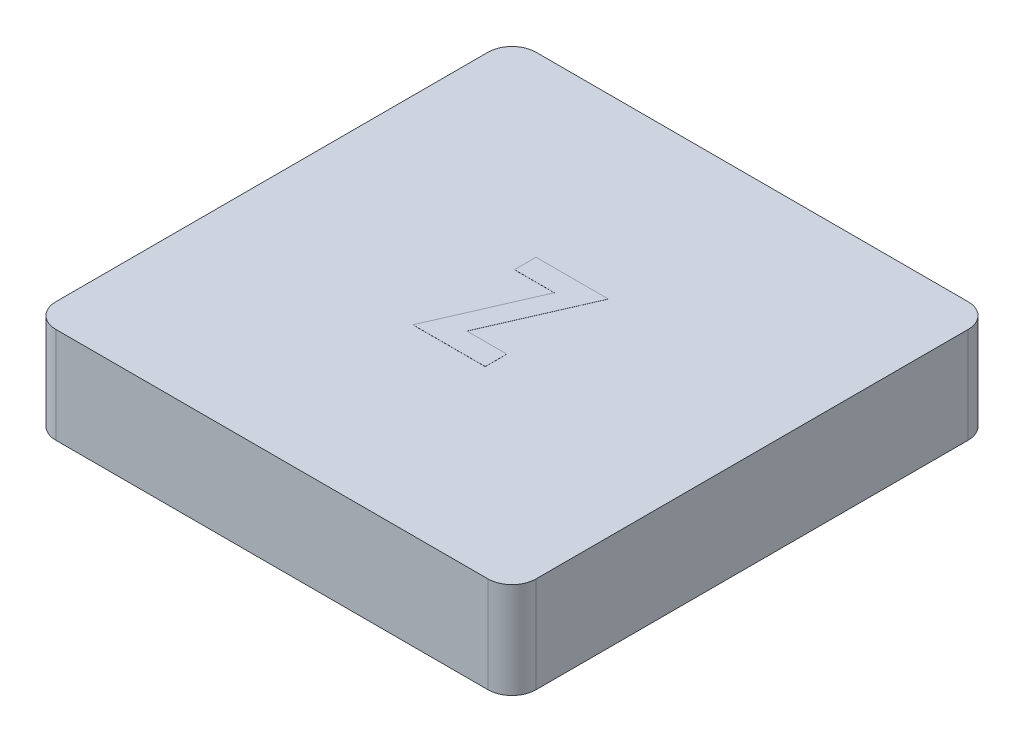
SolidWorks part; units mm, degrees
ref_plane "Front Plane" through (0, 0, 0) normal (0, 0, 1) x (1, 0, 0)
ref_plane "Top Plane" through (0, 0, 0) normal (0, 1, 0) x (1, 0, 0)
ref_plane "Right Plane" through (0, 0, 0) normal (1, 0, 0) x (0, 0, -1)
sketch "Sketch1" plane through (0, 0, 0) normal (0, 1, 0) x (1, 0, 0)
  line L0 (0, 0) -> (12.7, 0)
  line L1 (12.7, 0) -> (12.7, 12.7)
  line L2 (12.7, 12.7) -> (0, 12.7)
  line L3 (0, 12.7) -> (0, 0)
  dimension "D1" = 12.7
  dimension "D2" = 12.7
extrude "Boss-Extrude1" add sketch "Sketch1" along normal blind 2.54
fillet "Fillet1" radius 0.635 4 edges at (0, 1.27, -12.7) (12.7, 1.27, -12.7) (12.7, 1.27, 0) (0, 1.27, 0)
shell "Shell1" thickness 0.635 removed face at (6.35, 0, -6.35)
sketch "Sketch2" plane through (0, 1.905, 0) normal (0, -1, 0) x (-1, 0, 0)
  line L0 (-0.635, 6.35) -> (-12.065, 6.35) construction
  line L1 (-0.635, 12.065) -> (-0.635, 0.635) construction
  line L2 (-12.065, 0.635) -> (-12.065, 12.065) construction
  line L3 (-6.35, 0.635) -> (-6.35, 12.065) construction
  line L4 (-0.635, 0.635) -> (-12.065, 0.635) construction
  line L5 (-12.065, 12.065) -> (-0.635, 12.065) construction
  circle A0 centre (-6.35, 6.35) radius 2.54
  dimension "D1" = 5.08
extrude "Boss-Extrude2" add sketch "Sketch2" along normal up to surface (1.905 mm away) up to face at (6.35, 0, -6.35)
sketch "Sketch3" plane through (0, 2.54, 0) normal (0, 1, 0) x (1, 0, 0)
  line L0 (0, 12.065) -> (0, 0.635) construction
  line L1 (0.635, 0) -> (12.065, 0) construction
  text T0 "<b>Z</b>"
  point P1 (0, 0)
  dimension "D1" = 5.1308
  dimension "D2" = 4.826
extrude "Boss-Extrude3" add sketch "Sketch3" along normal blind 0.0025
